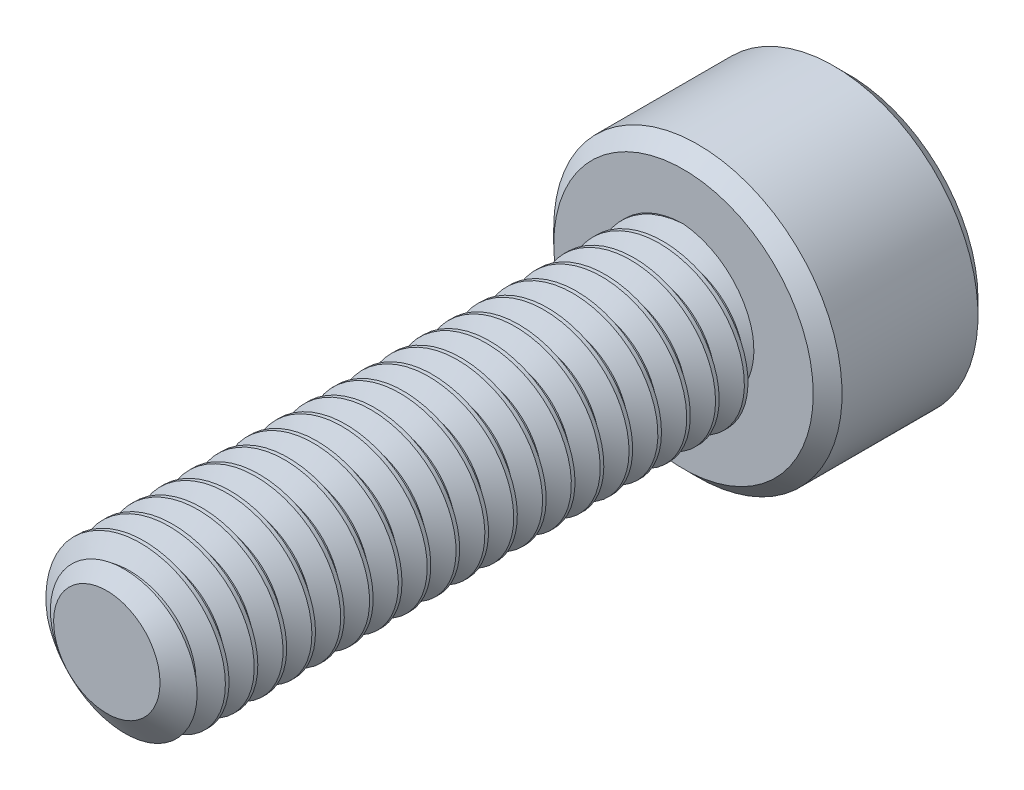
SolidWorks part; units mm, degrees
note: '?' marks a value the reader was unsure of.
other "DetailItem1"
material "AISI 316 Annealed Stainless Steel Bar (SS)"
ref_plane "Front Plane" through (0, 0, 0) normal (0, 0, 1) x (1, 0, 0)
ref_plane "Top Plane" through (0, 0, 0) normal (0, 1, 0) x (1, 0, 0)
ref_plane "Right Plane" through (0, 0, 0) normal (1, 0, 0) x (0, 0, -1)
sketch "Sketch1" plane through (0, 0, 0) normal (0, 0, 1) x (1, 0, 0)
  circle A0 centre (0, 0) radius 2
  dimension "OD" = 4
extrude "Extrude1" add sketch "Sketch1" against normal blind 14
sketch "Sketch2" plane through (0, 0, 0) normal (0, 0, 1) x (1, 0, 0)
  circle A0 centre (0, 0) radius 2 construction
  circle A1 centre (0, 0) radius 2
curve "Helix/Spiral1" pitch 0.7 height 14.7 radius 2 centre (0, 0, 0) axis (0, 0, -1) start towards (0, 1, 0) parameters "pitch"=0.7
sketch "Sketch3" plane through (0, 0, 0) normal (1, 0, 0) x (0, 0, -1)
  line L0 (-0.6125, 2) -> (-0.35, 1.5453)
  line L1 (-0.35, 1.5453) -> (-0.2625, 1.5453)
  line L2 (-0.2625, 1.5453) -> (0, 2)
  line L3 (-0.6125, 2) -> (0, 2)
  line L4 (-0.3063, 2) -> (-0.3063, 1.5453) construction
  line L5 (-0.4813, 1.7727) -> (-0.1313, 1.7727) construction
  line L6 (0, 2) -> (0, -2) construction
  dimension "D1" = 0.0875
  dimension "D2" = 0.35
  dimension "D3" = 60
sweep "Cut-Sweep1" cut profiles "Sketch3" path "Helix/Spiral1" align with end faces yes
sketch "Sketch4" plane through (0, 0, 0) normal (1, 0, 0) x (0, 0, -1)
  line L0 (0.4962, 2) -> (0, 1.2913)
  line L1 (0, 1.2913) -> (0, 2)
  line L2 (0.4962, 2) -> (0, 2)
  line L3 (-0.6125, 2) -> (0, 2) construction
  line L4 (0, 0) -> (7.0209, 0) construction
  dimension "D1" = 55
  dimension "D2" = 0.254
revolve "Cut-Revolve1" cut sketch "Sketch4" angle 360 about L4
sketch "Sketch6" plane through (0, 0, -14) normal (0, 0, -1) x (-1, 0, 0)
  circle A0 centre (0, 0) radius 3.5
  dimension "head dia" = 7
extrude "Extrude2" add sketch "Sketch6" along normal blind 4
sketch "Sketch7" plane through (0, 0, -18) normal (0, 0, -1) x (-1, 0, 0)
  line L1 (0, 1.7321) -> (-1.5, 0.866)
  line L2 (-1.5, 0.866) -> (-1.5, -0.866)
  line L3 (-1.5, -0.866) -> (0, -1.7321)
  line L4 (0, -1.7321) -> (1.5, -0.866)
  line L5 (1.5, -0.866) -> (1.5, 0.866)
  line L6 (1.5, 0.866) -> (0, 1.7321)
  circle A0 centre (0, 0) radius 1.5 construction
  dimension "hex dia" = 3
extrude "Cut-Extrude1" cut sketch "Sketch7" against normal blind 2.25
sketch "Sketch8" plane through (0, 0, -18) normal (0, 0, -1) x (-1, 0, 0)
  circle A0 centre (0, 0) radius 1.7321
extrude "Cut-Extrude2" cut sketch "Sketch8" against normal through all draft 45
chamfer "Chamfer1" distance 0.35 angle 45 2 edges at (-3.5, 0, -18) (-3.5, 0, -14)
sketch "Sketch10" plane through (0, 0, -14) normal (0, 0, 1) x (1, 0, 0)
  circle A1 centre (0, 0) radius 2
  circle A2 centre (0, 0) radius 2
  dimension "D1" = 0
ref_plane "Plane1" through (0, 0, 0) normal (0, 0, 1) x (1, 0, 0)
extrude "partial thread" [suppressed] add sketch "Sketch10" along normal up to surface (36 mm away) separate body
chamfer "Chamfer2" [suppressed] distance 0.08 angle 45
combine bodies "Combine1" [suppressed] operation type? add bodies to combine 107 108
sketch "Sketch9" plane through (0, 0, 0) normal (1, 0, 0) x (0, 0, -1)
  line L0 (0, 2) -> (0, -2) construction
  line L1 (1.75, 2) -> (1.75, -2) construction
  dimension "D1" = 1.75
equation "\"D3@Helix/Spiral1\" = \"screw length@Extrude1\"+\"pitch@Helix/Spiral1\""
equation "\"D1@Sketch3\" = \"pitch@Helix/Spiral1\"*.125"
equation "\"D2@Sketch3\" = \"pitch@Helix/Spiral1\"*.5"
equation "\"D1@Cut-Extrude1\" = \"hex dia@Sketch7\"*.75"
equation "\"D1@Chamfer1\" = \"head dia@Sketch6\"*.05"
equation "\"D1@Sketch9\" = \"pitch@Helix/Spiral1\"*2.5"
equation "\"D1@Chamfer2\"=\"OD@Sketch1\"*.02"
